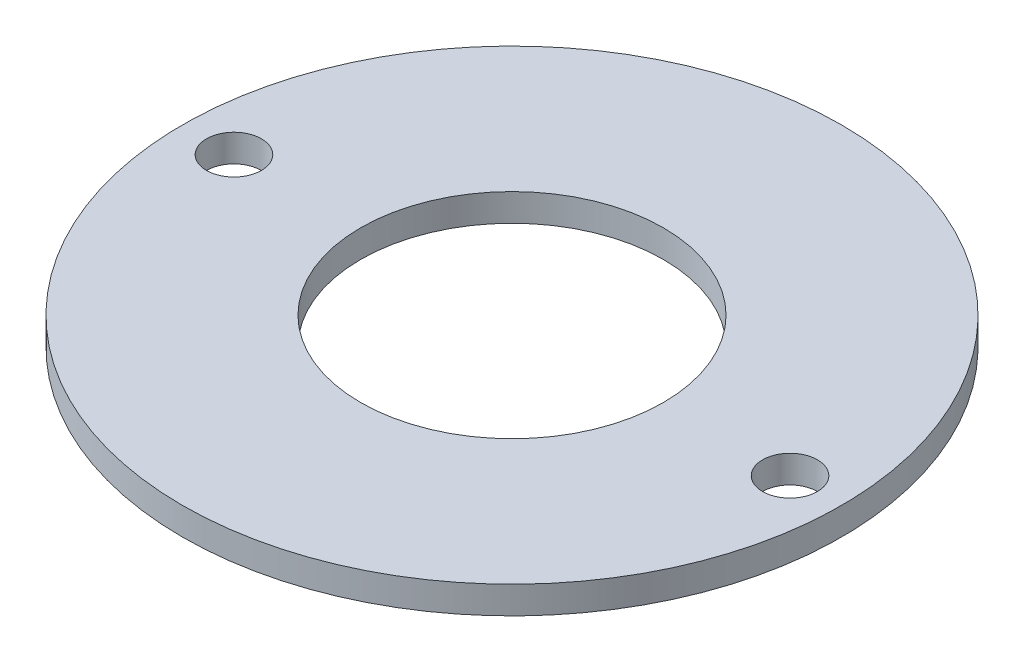
SolidWorks part; units mm, degrees
ref_plane "Front Plane" through (0, 0, 0) normal (0, 0, 1) x (1, 0, 0)
ref_plane "Top Plane" through (0, 0, 0) normal (0, 1, 0) x (1, 0, 0)
ref_plane "Right Plane" through (0, 0, 0) normal (1, 0, 0) x (0, 0, -1)
sketch "Sketch1" plane through (0, 0, 0) normal (0, 1, 0) x (1, 0, 0)
  circle A0 centre (0, 0) radius 76.2
  dimension "D1" = 152.4
extrude "Boss-Extrude1" add sketch "Sketch1" along normal blind 6.35
sketch "Sketch2" plane through (0, 6.35, 0) normal (0, 1, 0) x (1, 0, 0)
  circle A0 centre (0, 0) radius 35
  dimension "D1" = 70
extrude "Cut-Extrude1" cut sketch "Sketch2" against normal blind 6.35
sketch "Sketch3" plane through (0, 6.35, 0) normal (0, 1, 0) x (1, 0, 0)
  line L0 (-76.2, 0) -> (76.2, 0) construction
  line L1 (-51.5875, 51.5875) -> (51.5875, 51.5875) construction
  line L2 (-51.5875, 51.5875) -> (-51.5875, -51.5875) construction
  line L3 (-51.5875, -51.5875) -> (51.5875, -51.5875) construction
  line L4 (51.5875, 51.5875) -> (51.5875, -51.5875) construction
  circle A0 centre (0, 0) radius 76.2 construction
  circle A1 centre (-64.2875, 0) radius 6.35
  circle A2 centre (64.2875, 0) radius 6.35
  dimension "D1" = 12.7
  dimension "D2" = 12.7
  dimension "D3" = 12.7
  dimension "D4" = 12.7
extrude "Cut-Extrude2" cut sketch "Sketch3" against normal blind 10
sketch "Sketch4" plane through (0, 6.35, 0) normal (0, 1, 0) x (1, 0, 0)
  line L1 (50, -50) -> (-50, -50) construction
  line L2 (50, -50) -> (50, 50) construction
  line L3 (50, 50) -> (-50, 50) construction
  line L4 (-50, -50) -> (-50, 50) construction
  line L5 (50, -50) -> (-50, 50) construction
  line L6 (50, 50) -> (-50, -50) construction
  point P0 (0, 0)
  dimension "D1" = 100
  dimension "D2" = 100
sketch "Sketch5" plane through (0, 6.35, 0) normal (0, 1, 0) x (1, 0, 0)
  line L0 (-50, 24.6) -> (-59.525, 24.6) construction
  line L1 (-50, -50) -> (-50, 50) construction
  line L2 (-50, -24.6) -> (-59.525, -24.6) construction
  line L3 (50, 50) -> (-50, 50) construction
  line L4 (50, -50) -> (-50, -50) construction
  line L5 (-50, 50) -> (50, -50) construction
  line L6 (-50, -50) -> (50, 50) construction
  line L7 (24.6, 50) -> (24.6, 59.525) construction
  line L8 (-50, 50) -> (50, 50) construction
  line L9 (-50, 50) -> (-50, -50) construction
  line L10 (-50, -50) -> (50, -50) construction
  line L11 (50, 50) -> (50, -50) construction
  line L12 (-24.6, 50) -> (-24.6, 59.525) construction
  line L13 (50, 24.6) -> (59.525, 24.6) construction
  line L14 (-24.6, -50) -> (-24.6, -59.525) construction
  line L15 (24.6, -50) -> (24.6, -59.525) construction
  line L16 (50, -24.6) -> (59.525, -24.6) construction
  dimension "D1" = 25.4
  dimension "D2" = 25.4
  dimension "D3" = 9.525
  dimension "D4" = 9.525
